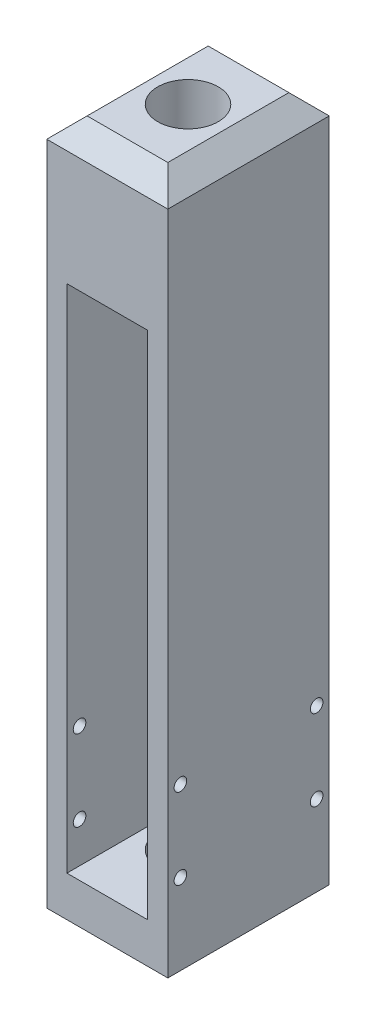
SolidWorks part; units mm, degrees
material "6061-T6 (SS)"
ref_plane "Front Plane" through (0, 0, 0) normal (0, 0, 1) x (1, 0, 0)
ref_plane "Top Plane" through (0, 0, 0) normal (0, 1, 0) x (1, 0, 0)
ref_plane "Right Plane" through (0, 0, 0) normal (1, 0, 0) x (0, 0, -1)
sketch "Sketch1" plane through (0, 0, 0) normal (0, 0, 1) x (1, 0, 0)
  line L1 (0, 0) -> (38.1, 0)
  line L2 (0, 0) -> (0, 215.9)
  line L3 (0, 215.9) -> (38.1, 215.9)
  line L4 (38.1, 0) -> (38.1, 215.9)
  line L5 (6.35, 12.7) -> (31.75, 12.7)
  line L6 (6.35, 12.7) -> (6.35, 173.355)
  line L7 (6.35, 173.355) -> (31.75, 173.355)
  line L8 (31.75, 12.7) -> (31.75, 173.355)
  dimension "D1" = 38.1
  dimension "D2" = 25.4
  dimension "D3" = 6.35
  dimension "D4" = 215.9
  dimension "D5" = 42.545
  dimension "D6" = 12.7
extrude "Boss-Extrude1" add sketch "Sketch1" along normal blind 50.8
hole_wizard "3/4 (0.75) Diameter Hole1" positions "Sketch2" profile "Sketch3" hole size "3/4" standard "ANSI Inch" end condition up to next
sketch "Sketch2" plane through (0, 0, 0) normal (0, -1, 0) x (-1, 0, 0)
  line L0 (0, 0) -> (-38.1, 0) construction
  line L1 (0, -50.8) -> (0, 0) construction
  point P0 (-19.05, -25.4)
  point P3 (0, 0)
  point P7 (-19.05, 0)
  point P8 (0, 0)
  point P11 (0, -25.4)
sketch "Sketch3" plane through (19.05, 0, 25.4) normal (1, 0, 0) x (0, 0, -1)
  line L0 (0, 0) -> (0, 12.7)
  line L1 (0, 12.7) -> (9.525, 12.7)
  line L2 (9.525, 12.7) -> (9.525, 0)
  line L5 (9.525, 0) -> (0, 0)
  line L11 (0, -6.35) -> (0, 107.95) construction
  dimension "Thru Hole Dia." = 19.05
  dimension "Thru Hole Depth" = 12.7
hole_wizard "3/4 (0.75) Diameter Hole2" positions "Sketch4" profile "Sketch5" hole size "3/4" standard "ANSI Inch" end condition up to next
sketch "Sketch4" plane through (0, 215.9, 0) normal (0, 1, 0) x (1, 0, 0)
  line L0 (38.1, -50.8) -> (0, -50.8) construction
  line L1 (0, -50.8) -> (0, 0) construction
  point P0 (19.05, -25.4)
  point P3 (0, 0)
  point P6 (19.05, -50.8)
  point P9 (0, -25.4)
sketch "Sketch5" plane through (19.05, 215.9, 25.4) normal (1, 0, 0) x (0, 0, 1)
  line L0 (0, 0) -> (0, 42.545)
  line L1 (0, 42.545) -> (9.525, 42.545)
  line L2 (9.525, 42.545) -> (9.525, 0)
  line L5 (9.525, 0) -> (0, 0)
  line L11 (0, -6.35) -> (0, 107.95) construction
  dimension "Thru Hole Dia." = 19.05
  dimension "Thru Hole Depth" = 42.545
hole_wizard "5/32 (0.15625) Diameter Hole1" positions "Sketch6" profile "Sketch7" hole size "5/32" standard "ANSI Inch" end condition up to next
sketch "Sketch6" plane through (38.1, 0, 0) normal (1, 0, 0) x (0, 0, -1)
  line L0 (-50.8, 0) -> (0, 0) construction
  line L2 (-50.8, 0) -> (-50.8, 215.9) construction
  point P0 (-46.8312, 25.4)
  point P2 (-3.9688, 25.4)
  point P4 (-3.9688, 50.8)
  point P6 (-46.8312, 50.8)
  point P9 (0, 0)
  point P10 (0, 0)
  point P11 (0, 0)
  point P12 (0, 0)
  point P13 (0, 0)
  point P18 (0, 0)
  dimension "D1" = 25.4
  dimension "D2" = 42.8625
  dimension "D3" = 25.4
  dimension "D4" = 3.9688
sketch "Sketch7" plane through (38.1, 25.4, 46.8312) normal (0, 1, 0) x (0, 0, -1)
  line L0 (0, 0) -> (0, 38.1)
  line L1 (0, 38.1) -> (1.9844, 38.1)
  line L2 (1.9844, 38.1) -> (1.9844, 0)
  line L5 (1.9844, 0) -> (0, 0)
  line L11 (0, -6.35) -> (0, 107.95) construction
  dimension "Thru Hole Dia." = 3.9688
  dimension "Thru Hole Depth" = 38.1
ref_plane "Plane1" through (19.05, 0, 0) normal (1, 0, 0) x (0, 0, -1)
mirror "Mirror1" about plane through (19.05, 0, 0) normal (1, 0, 0) of "5/32 (0.15625) Diameter Hole1"
chamfer "Chamfer1" distance 6.35 angle 45 4 edges at (19.05, 215.9, 0) (0, 215.9, 25.4) (38.1, 215.9, 25.4) (19.05, 215.9, 50.8)
